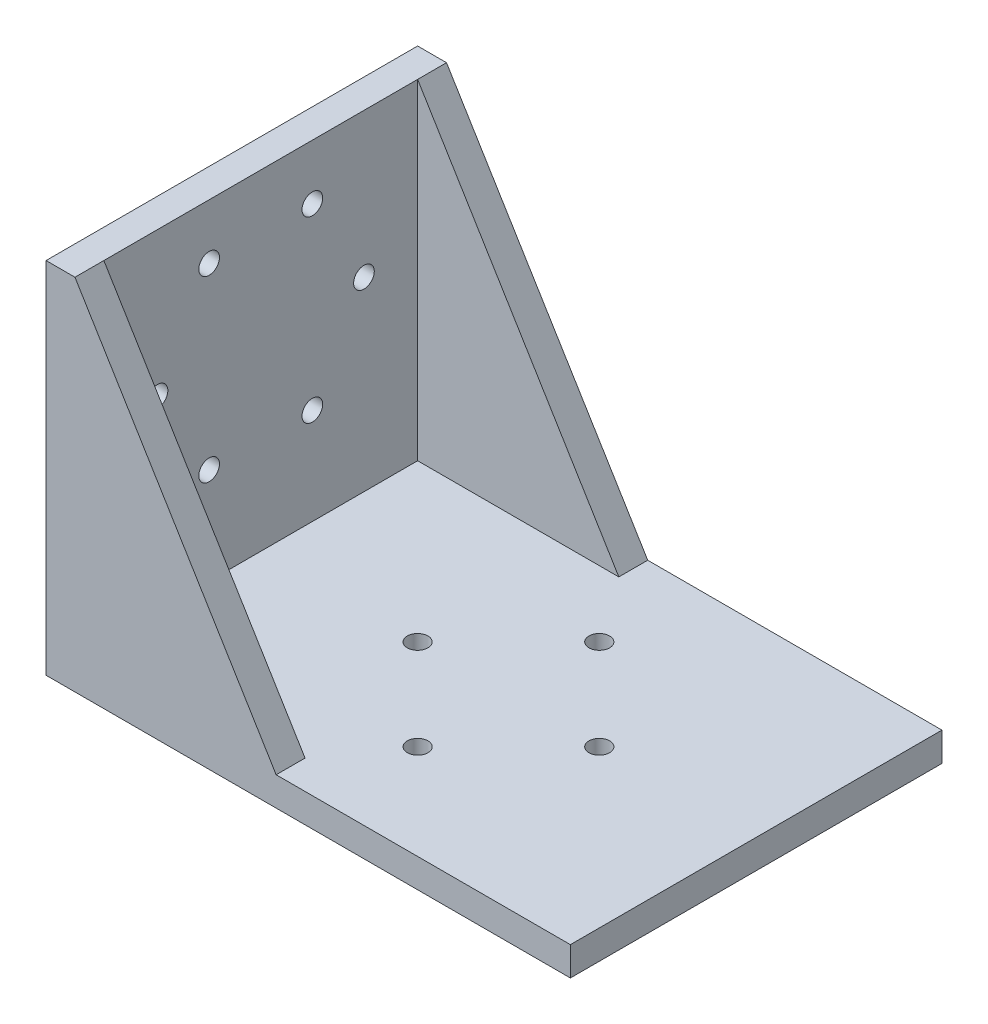
SolidWorks part; units mm, degrees
ref_plane "前视基准面" through (0, 0, 0) normal (0, 0, 1) x (1, 0, 0)
ref_plane "上视基准面" through (0, 0, 0) normal (0, 1, 0) x (1, 0, 0)
ref_plane "右视基准面" through (0, 0, 0) normal (1, 0, 0) x (0, 0, -1)
sketch "草图1" plane through (0, 0, 0) normal (0, 1, 0) x (1, 0, 0)
  line L1 (0, 0) -> (120, 0)
  line L2 (0, 0) -> (0, 70)
  line L3 (0, 70) -> (120, 70)
  line L4 (120, 0) -> (120, 70)
extrude "凸台-拉伸1" add sketch "草图1" along normal blind 7
sketch "草图2" plane through (0, 7, 0) normal (0, 1, 0) x (1, 0, 0)
  circle A0 centre (82, 35) radius 2.5
  circle A1 centre (60, 13) radius 2.5
  circle A2 centre (38, 35) radius 2.5
  circle A3 centre (60, 57) radius 2.5
  point P12 (60, 35)
  dimension "D1" = 4
extrude "切除-拉伸2" cut sketch "草图2" against normal blind 7 contours A2 | A1 | A0 | A3
sketch "草图5" plane through (0, 0, 0) normal (-1, 0, 0) x (0, 0, 1)
  line L1 (-70, 0) -> (0, 0)
  line L2 (-70, 0) -> (-70, 87)
  line L3 (-70, 87) -> (0, 87)
  line L4 (0, 0) -> (0, 87)
extrude "凸台-拉伸4" add sketch "草图5" along normal blind 7
sketch "草图6" plane through (-7, 0, 0) normal (-1, 0, 0) x (0, 0, 1)
  circle A0 centre (-10, 52) radius 2.5
  circle A1 centre (-22.5, 30.3494) radius 2.5
  circle A2 centre (-47.5, 30.3494) radius 2.5
  circle A3 centre (-60, 52) radius 2.5
  circle A4 centre (-47.5, 73.6506) radius 2.5
  circle A5 centre (-22.5, 73.6506) radius 2.5
  point P18 (-35, 52)
  dimension "D1" = 6
extrude "切除-拉伸3" cut sketch "草图6" against normal blind 7
sketch "草图7" plane through (0, 0, 0) normal (0, 0, 1) x (1, 0, 0)
  line L0 (0, 87) -> (0, 7)
  line L1 (0, 7) -> (0, 87) construction
  line L2 (0, 7) -> (120, 7)
  line L3 (120, 7) -> (120, 0)
  line L4 (120, 0) -> (-7, 0)
  line L5 (-7, 0) -> (-7, 87)
  line L6 (-7, 87) -> (0, 87)
extrude "凸台-拉伸5" add sketch "草图7" along normal blind 10
sketch "草图8" plane through (0, 0, -70) normal (0, 0, -1) x (-1, 0, 0)
  line L0 (7, 87) -> (7, 0)
  line L1 (7, 0) -> (-120, 0)
  line L2 (-120, 0) -> (-120, 7)
  line L3 (-120, 7) -> (0, 7)
  line L4 (0, 7) -> (0, 87)
  line L5 (0, 87) -> (7, 87)
extrude "凸台-拉伸6" add sketch "草图8" along normal blind 10
sketch "草图9" plane through (0, 0, -80) normal (0, 0, -1) x (-1, 0, 0)
  line L0 (7, 0) -> (-53, 0)
  line L1 (-120, 0) -> (7, 0) construction
  line L2 (-53, 0) -> (0, 87)
  line L3 (0, 87) -> (7, 0)
extrude "凸台-拉伸7" add sketch "草图9" against normal blind 7
sketch "草图10" plane through (0, 0, 10) normal (0, 0, 1) x (1, 0, 0)
  line L0 (-7, 0) -> (53, 0)
  line L1 (-7, 0) -> (120, 0) construction
  line L2 (53, 0) -> (0, 87)
  line L3 (0, 87) -> (-7, 0)
extrude "凸台-拉伸8" add sketch "草图10" against normal blind 7
